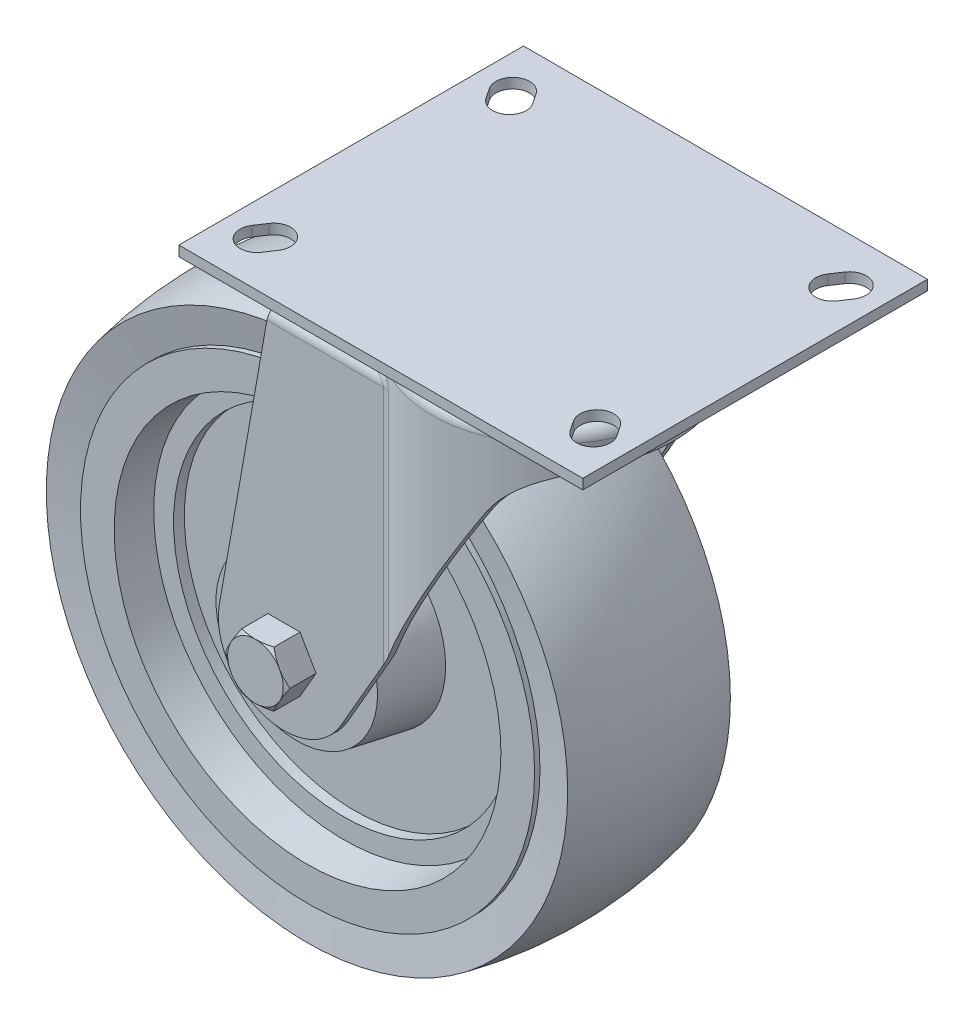
SolidWorks part; units mm, degrees
ref_plane "Front Plane" through (0, 0, 0) normal (0, 0, 1) x (1, 0, 0)
ref_plane "Top Plane" through (0, 0, 0) normal (0, 1, 0) x (1, 0, 0)
ref_plane "Right Plane" through (0, 0, 0) normal (1, 0, 0) x (0, 0, -1)
sketch "Sketch1" plane through (0, 0, 0) normal (0, 0, 1) x (1, 0, 0)
  line L0 (0, 0) -> (0, -150.8125)
  line L1 (-47.625, 0) -> (47.625, 0)
  line L2 (-47.625, 0) -> (-47.625, -2.3813)
  line L3 (-47.625, -2.3813) -> (47.625, -2.3813)
  line L4 (47.625, 0) -> (47.625, -2.3813)
  line L5 (0, -150.8125) -> (-38.862, -150.8125)
  line L6 (0, -12.3031) -> (-28.575, -12.3031)
  line L7 (-28.575, -12.3031) -> (-28.575, -10.3187)
  line L8 (-25.4, -7.1437) -> (0, -7.1438)
  line L9 (0, -7.1438) -> (0, -12.3031)
  line L10 (-25.4, -7.1437) -> (-24.5201, -5.6198)
  line L11 (-18.9109, -2.3813) -> (0, -2.3813)
  line L12 (-27.051, -12.3031) -> (-27.051, -13.8271)
  line L13 (-27.051, -13.8271) -> (0, -13.8271)
  line L14 (-25.4576, -95.0516) -> (10.6508, -32.51)
  line L15 (-35.0813, -80.7641) -> (-42.6427, -80.7641)
  line L16 (-42.6427, -80.7641) -> (-46.4235, -87.3125)
  line L17 (-46.4235, -87.3125) -> (-42.6427, -93.8609)
  line L18 (-42.6427, -93.8609) -> (-35.0813, -93.8609)
  line L19 (-35.0813, -93.8609) -> (-31.3005, -87.3125)
  line L20 (-31.3005, -87.3125) -> (-35.0813, -80.7641)
  line L21 (28.575, -22.1615) -> (0, -22.1615) construction
  line L22 (28.575, -22.1615) -> (28.575, -13.8271)
  line L23 (-38.862, -87.3125) -> (-38.862, -48.9313) construction
  line L24 (-54.105, -84.6248) -> (-42.3201, -17.7895)
  line L25 (-42.3201, -17.7895) -> (-28.575, -17.7895)
  line L26 (-28.575, -17.7895) -> (-28.575, -13.8271)
  circle A0 centre (-38.862, -87.3125) radius 63.5
  arc A1 (-28.575, -10.3187) -> (-25.4, -7.1437) centre (-25.4, -10.3187) cw
  arc A2 (-24.5201, -5.6198) -> (-18.9109, -2.3813) centre (-18.9109, -8.8582) cw
  circle A3 centre (-38.862, -87.3125) radius 15.4781
  circle A4 centre (-38.862, -87.3125) radius 6.5484 construction
  arc A5 (10.6508, -32.51) -> (28.575, -22.1615) centre (28.575, -42.8586) cw
  dimension "Wheel Dia" = 127
  dimension "D14" = 13.0969
  dimension "D15" = 30.9562
  dimension "Height" = 150.8125
  dimension "Plate Length" = 95.25
  dimension "Plate Thickness" = 2.3813
  dimension "Swivel Radius" = 102.362
  dimension "D6" = 5.1594
  dimension "D7" = 3.175
  dimension "D8" = 28.575
  dimension "D9" = 4.7625
  dimension "D10" = 60
  dimension "D11" = 1.524
  dimension "D12" = 1.524
  dimension "D13" = 1.524
  dimension "D16" = 8.3344
  dimension "D17" = 28.575
  dimension "D18" = 30
  dimension "D19" = 10
  dimension "D20" = 3.9624
sketch "Sketch2" plane through (0, 0, 0) normal (0, 0, 1) x (1, 0, 0)
  line L1 (-47.625, -2.3813) -> (47.625, -2.3813)
  line L2 (-47.625, -2.3813) -> (-47.625, 0)
  line L3 (-47.625, 0) -> (47.625, 0)
  line L4 (47.625, -2.3813) -> (47.625, 0)
extrude "Boss-Extrude1" add sketch "Sketch2" along normal mid plane 81.28
sketch "Sketch3" plane through (0, 0, 0) normal (0, 1, 0) x (1, 0, 0)
  line L0 (38.1, 27.7812) -> (39.6875, 30.1625) construction
  line L1 (34.7978, 29.9827) -> (36.3853, 32.364)
  line L2 (41.4022, 25.5798) -> (42.9897, 27.961)
  line L3 (0, 0) -> (0, 40.64) construction
  line L4 (47.625, 40.64) -> (-47.625, 40.64) construction
  line L5 (0, 0) -> (50.0062, 0) construction
  line L6 (-47.625, 0) -> (47.625, 0) construction
  line L7 (-38.1, 27.7812) -> (-39.6875, 30.1625) construction
  line L8 (-34.7978, 29.9827) -> (-36.3853, 32.364)
  line L9 (-41.4022, 25.5798) -> (-42.9897, 27.961)
  line L10 (-38.1, -27.7812) -> (-39.6875, -30.1625) construction
  line L11 (-34.7978, -29.9827) -> (-36.3853, -32.364)
  line L12 (-41.4022, -25.5798) -> (-42.9897, -27.961)
  line L13 (38.1, -27.7812) -> (39.6875, -30.1625) construction
  line L14 (34.7978, -29.9827) -> (36.3853, -32.364)
  line L15 (41.4022, -25.5798) -> (42.9897, -27.961)
  arc A0 (34.7978, 29.9827) -> (41.4022, 25.5798) centre (38.1, 27.7812) ccw
  arc A1 (42.9897, 27.961) -> (36.3853, 32.364) centre (39.6875, 30.1625) ccw
  arc A2 (-34.7978, 29.9827) -> (-41.4022, 25.5798) centre (-38.1, 27.7812) cw
  arc A3 (-42.9897, 27.961) -> (-36.3853, 32.364) centre (-39.6875, 30.1625) cw
  arc A4 (-34.7978, -29.9827) -> (-41.4022, -25.5798) centre (-38.1, -27.7812) ccw
  arc A5 (-42.9897, -27.961) -> (-36.3853, -32.364) centre (-39.6875, -30.1625) ccw
  arc A6 (34.7978, -29.9827) -> (41.4022, -25.5798) centre (38.1, -27.7812) cw
  arc A7 (42.9897, -27.961) -> (36.3853, -32.364) centre (39.6875, -30.1625) cw
  point P2 (38.8938, 28.9719)
  point P17 (-38.8938, 28.9719)
  point P24 (-38.8938, -28.9719)
  point P31 (38.8938, -28.9719)
  dimension "D2" = 76.2
  dimension "D3" = 79.375
  dimension "D5" = 60.325
  dimension "D1" = 7.9375
  dimension "D4" = 55.5625
extrude "Cut-Extrude1" cut sketch "Sketch3" against normal blind 85.725
ref_plane "Plane1" through (-38.862, 0, 0) normal (1, 0, 0) x (0, 0, -1)
sketch "Sketch4" plane through (-38.862, 0, 0) normal (1, 0, 0) x (0, 0, -1)
  line L1 (19.05, -23.8125) -> (-19.05, -23.8125) construction
  line L2 (19.05, -23.8125) -> (19.05, -87.3125) construction
  line L3 (19.05, -87.3125) -> (-19.05, -87.3125) construction
  line L4 (-19.05, -23.8125) -> (-19.05, -87.3125) construction
  line L5 (0, -23.8125) -> (0, -150.8125) construction
  line L6 (-21.59, -87.3125) -> (-21.59, -68.2625)
  line L7 (-21.59, -68.2625) -> (-7.9375, -65.8552)
  line L8 (-7.9375, -65.8552) -> (-7.9375, -47.1466)
  line L9 (-7.9375, -47.1466) -> (-10.4775, -47.1466)
  line L10 (-10.4775, -47.1466) -> (-10.4775, -42.4695)
  line L11 (-10.4775, -42.4695) -> (-19.05, -41.7195)
  line L12 (-19.05, -41.7195) -> (-19.05, -33.782)
  line L13 (-19.05, -33.782) -> (-17.78, -33.782)
  line L14 (-17.78, -33.782) -> (-19.1796, -25.8445)
  line L15 (0, 0) -> (0, -150.8125) construction
  line L16 (0, -23.8125) -> (0, -115.3445) construction
  line L17 (17.78, -33.782) -> (19.1796, -25.8445)
  line L18 (19.05, -33.782) -> (17.78, -33.782)
  line L19 (19.05, -41.7195) -> (19.05, -33.782)
  line L20 (10.4775, -42.4695) -> (19.05, -41.7195)
  line L21 (10.4775, -47.1466) -> (10.4775, -42.4695)
  line L22 (7.9375, -47.1466) -> (10.4775, -47.1466)
  line L23 (7.9375, -65.8552) -> (7.9375, -47.1466)
  line L24 (21.59, -68.2625) -> (7.9375, -65.8552)
  line L25 (21.59, -68.2625) -> (21.59, -87.3125)
  line L26 (-21.59, -87.3125) -> (21.59, -87.3125)
  arc A0 (-19.1796, -25.8445) -> (19.1796, -25.8445) centre (0, -115.3445) cw
  point P7 (0, -23.8125)
  dimension "Wheel Width" = 38.1
  dimension "D2" = 2.54
  dimension "D3" = 15.875
  dimension "D4" = 7.9375
  dimension "D5" = 1.27
  dimension "D6" = 10
  dimension "D7" = 2.54
  dimension "D8" = 38.1
  dimension "D9" = 10
  dimension "D10" = 5
  dimension "D11" = 7.9375
  dimension "D12" = 2.032
  dimension "D13" = 23.3857
  dimension "D14" = 4.6771
revolve "Revolve1" add sketch "Sketch4" angle 360 about L26
sketch "Sketch5" plane through (0, 0, 0) normal (0, 0, 1) x (1, 0, 0)
  line L0 (-27.051, -13.8271) -> (0, -13.8271) construction
  line L1 (0, -12.3031) -> (-28.575, -12.3031) construction
  line L2 (-27.051, -13.8271) -> (0, -13.8271)
  line L3 (-27.051, -12.3031) -> (-28.575, -12.3031)
  line L4 (-25.4, -7.1437) -> (-24.5201, -5.6198) construction
  line L5 (-25.4, -7.1437) -> (-24.5201, -5.6198)
  line L6 (-28.575, -10.3187) -> (-28.575, -12.3031)
  line L7 (-27.051, -13.8271) -> (-27.051, -12.3031)
  line L8 (0, -13.8271) -> (0, -2.3813)
  line L9 (0, -2.3813) -> (-18.9109, -2.3813)
  arc A0 (-25.4, -7.1437) -> (-28.575, -10.3187) centre (-25.4, -10.3187) ccw construction
  arc A1 (-18.9109, -2.3813) -> (-24.5201, -5.6198) centre (-18.9109, -8.8582) ccw construction
  arc A2 (-25.4, -7.1437) -> (-28.575, -10.3187) centre (-25.4, -10.3187) ccw
  arc A3 (-18.9109, -2.3813) -> (-24.5201, -5.6198) centre (-18.9109, -8.8582) ccw
revolve "Revolve2" add sketch "Sketch5" angle 360 about L8
sketch "Sketch6" plane through (0, -13.8271, 0) normal (0, -1, 0) x (1, 0, 0)
  circle A0 centre (0, 0) radius 28.575
extrude "Boss-Extrude2" add sketch "Sketch6" along normal up to vertex (136.9854 mm away) separate body up to point (0, -150.8125, 0)
sketch "Sketch7" plane through (0, 0, 0) normal (0, 0, 1) x (1, 0, 0)
  line L0 (-42.3201, -17.7895) -> (-28.575, -17.7895) construction
  line L1 (-60.455, -17.7895) -> (0, -17.7895)
  line L2 (-60.455, -17.7895) -> (-60.455, -150.8125)
  line L3 (-60.455, -150.8125) -> (0, -150.8125)
  line L4 (0, -17.7895) -> (0, -150.8125)
  dimension "D1" = 6.35
extrude "Boss-Extrude3" add sketch "Sketch7" along normal mid plane 49.2125 separate body
fillet "Fillet1" radius 3.175 2 edges at (-30.2275, -17.7895, 24.6063) (-30.2275, -17.7895, -24.6063)
fillet "Fillet2" radius 3.175 1 edges at (28.575, -13.8271, 0)
combine bodies "Combine1" operation type add bodies to combine 105 106
fillet "Fillet3" radius 3.175 5 edges at (-14.528, -85.8885, -24.6063) (-14.8682, -19.8447, -24.4022) (-28.575, -17.7895, 0) (-15.5609, -19.0531, 23.9664) (-14.528, -85.8885, 24.6063)
shell "Shell1" thickness 1.5875
sketch "Sketch8" plane through (0, 0, 0) normal (0, 0, 1) x (1, 0, 0)
  line L0 (-54.105, -84.6248) -> (-42.3201, -17.7895) construction
  line L1 (-25.4576, -95.0516) -> (10.6508, -32.51) construction
  line L2 (-54.105, -84.6248) -> (-42.3201, -17.7895)
  line L3 (-25.4576, -95.0516) -> (10.6508, -32.51)
  circle A0 centre (-38.862, -87.3125) radius 15.4781 construction
  arc A1 (28.575, -22.1615) -> (10.6508, -32.51) centre (28.575, -42.8586) ccw construction
  arc A2 (-54.105, -84.6248) -> (-25.4576, -95.0516) centre (-38.862, -87.3125) ccw
  arc A3 (28.575, -22.1615) -> (10.6508, -32.51) centre (28.575, -42.8586) ccw
extrude "Cut-Extrude2" cut sketch "Sketch8" against normal through all and the other way through all flip side to cut
sketch "Sketch9" plane through (0, 0, 0) normal (0, 0, 1) x (1, 0, 0)
  circle A0 centre (-38.862, -87.3125) radius 4.7625
  dimension "D1" = 9.525
extrude "Boss-Extrude4" add sketch "Sketch9" along normal up to surface (24.6062 mm away) separate body up to face at (-31.5118, -62.2411, 24.6063)
sketch "Sketch10" plane through (0, 0, 24.6063) normal (0, 0, 1) x (1, 0, 0)
  line L0 (-42.6427, -80.7641) -> (-46.4235, -87.3125) construction
  line L1 (-46.4235, -87.3125) -> (-42.6427, -93.8609) construction
  line L2 (-42.6427, -93.8609) -> (-35.0813, -93.8609) construction
  line L3 (-35.0813, -93.8609) -> (-31.3005, -87.3125) construction
  line L4 (-31.3005, -87.3125) -> (-35.0813, -80.7641) construction
  line L5 (-35.0813, -80.7641) -> (-42.6427, -80.7641) construction
  line L6 (-42.6427, -80.7641) -> (-46.4235, -87.3125)
  line L7 (-46.4235, -87.3125) -> (-42.6427, -93.8609)
  line L8 (-42.6427, -93.8609) -> (-35.0813, -93.8609)
  line L9 (-35.0813, -93.8609) -> (-31.3005, -87.3125)
  line L10 (-31.3005, -87.3125) -> (-35.0813, -80.7641)
  line L11 (-35.0813, -80.7641) -> (-42.6427, -80.7641)
extrude "Boss-Extrude5" add sketch "Sketch10" along normal blind 6.731
sketch "Sketch11" plane through (0, 0, 31.3373) normal (0, 0, 1) x (1, 0, 0)
  circle A0 centre (-38.862, -87.3125) radius 6.5484 construction
  circle A1 centre (-38.862, -87.3125) radius 6.5484
extrude "Cut-Extrude3" cut sketch "Sketch11" against normal through all draft 60 flip side to cut
mirror "Mirror1" about plane through (0, 0, 0) normal (0, 0, 1) of bodies 111
combine bodies "Combine2" operation type add bodies to combine 108 104
combine bodies "Combine3" operation type add bodies to combine 113 112
equation "\"D14@Sketch4\" = \"D13@Sketch4\"/5"
equation "\"D1@Boss-Extrude3\" = \"Wheel Width@Sketch4\"+(\"Leg Thickness@Shell1\"*2)+.3125"
equation "\"D1@Fillet1\" = \"Leg Thickness@Shell1\"*2"
equation "\"D1@Fillet2\" = \"D1@Fillet1\""
equation "\"D1@Fillet3\" = \"D1@Fillet1\""
equation "\"D17@Sketch1\" = \"D8@Sketch1\""
